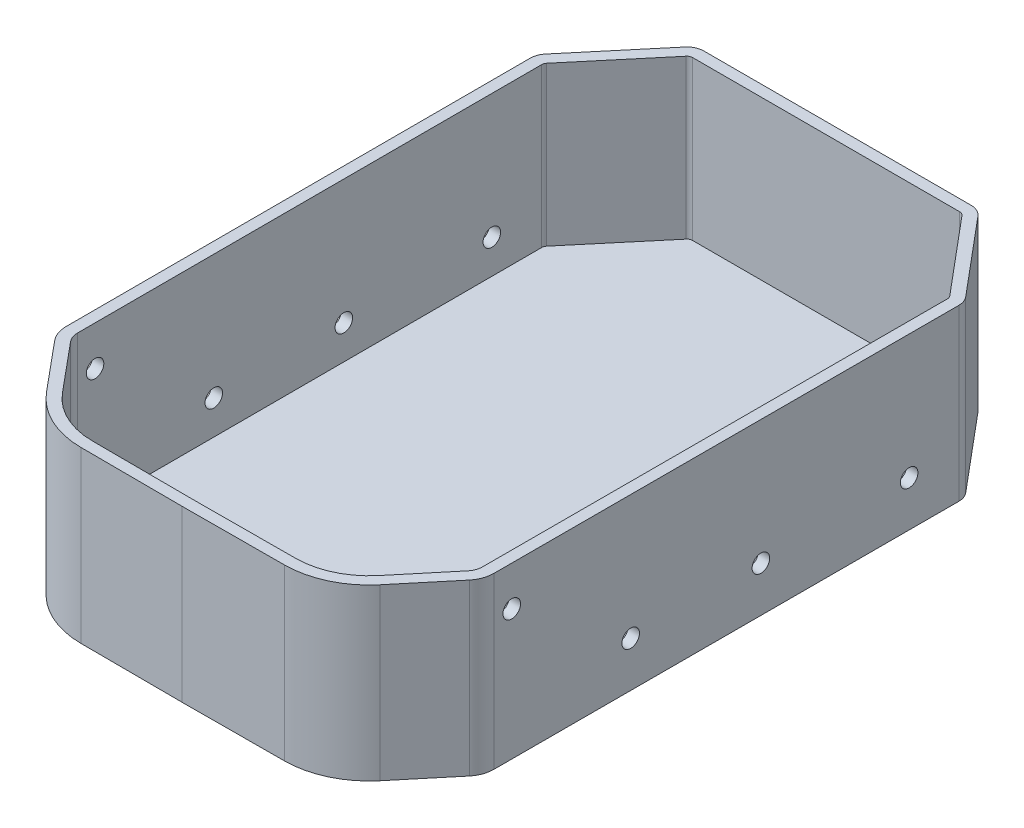
SolidWorks part; units mm, degrees
ref_plane "Ebene vorne" through (0, 0, 0) normal (0, 0, 1) x (1, 0, 0)
ref_plane "Ebene oben" through (0, 0, 0) normal (0, 1, 0) x (1, 0, 0)
ref_plane "Ebene rechts" through (0, 0, 0) normal (1, 0, 0) x (0, 0, -1)
sketch "Skizze1" plane through (0, 0, 0) normal (0, 1, 0) x (1, 0, 0)
  line L0 (-71.7828, 0) -> (65.2574, 0) construction
  line L1 (0, -55) -> (0, 55) construction
  line L2 (0, 50.8602) -> (0, -44.8504) construction
  line L4 (0, -75.745) -> (-24.9998, -75.6418)
  line L5 (-24.9998, -75.6418) -> (-37.7921, -60.2679)
  line L6 (-37.7921, -60.2679) -> (-37.8558, 24.7321)
  line L7 (-37.8558, 24.7321) -> (-25, 40.053)
  line L8 (-25, 40.053) -> (0, 40.053)
  line L9 (0, 40.053) -> (0, -75.745)
  dimension "D1" = 85
  dimension "D2" = 20
  dimension "D3" = 130
  dimension "D4" = 25
  dimension "D5" = 130
  dimension "D6" = 115.798
extrude "Aufsatz-Linear austragen1" add sketch "Skizze1" along normal blind 30
mirror "Spiegeln1" about plane through (0, 0, 0) normal (1, 0, 0) of "Aufsatz-Linear austragen1"
fillet "Verrundung11" radius 15 2 edges at (-24.9998, 15, 75.6418) (24.9998, 15, 75.6418)
fillet "Verrundung12" radius 5 2 edges at (37.7921, 15, 60.2679) (-37.7921, 15, 60.2679)
fillet "Verrundung13" radius 3 2 edges at (-25, 15, -40.053) (25, 15, -40.053)
fillet "Verrundung14" radius 3 2 edges at (37.8558, 15, -24.7321) (-37.8558, 15, -24.7321)
shell "Wandung4" thickness 2 removed face at (0, 30, 20.7928)
sketch "Skizze7" plane through (-37.8372, 0, 0.0283) normal (-1, 0, 0.0007) x (0.0007, 0, 1)
  line L0 (-23.6673, 30) -> (-23.6673, 0) construction
  line L1 (55, 0) -> (-55, 0) construction
  line L2 (-14.8473, 6.45) -> (-14.8473, 9.55) construction
  line L3 (-16.3973, 8) -> (-13.2973, 8) construction
  circle A0 centre (-14.8473, 8) radius 1.55
  circle A2 centre (11.3327, 8) radius 1.55
  circle A3 centre (34.3327, 8) radius 1.55
  circle A4 centre (55.3327, 23) radius 1.55
  dimension "D1" = 8.82
  dimension "D2" = 3.1
  dimension "D3" = 8
  dimension "D4" = 26.18
  dimension "D5" = 23
  dimension "D6" = 21
  dimension "D7" = 15
extrude "Schnitt-Linear austragen1" cut sketch "Skizze7" against normal up to surface (75.6944 mm away) up to face at (37.8242, 15, 17.4114)
